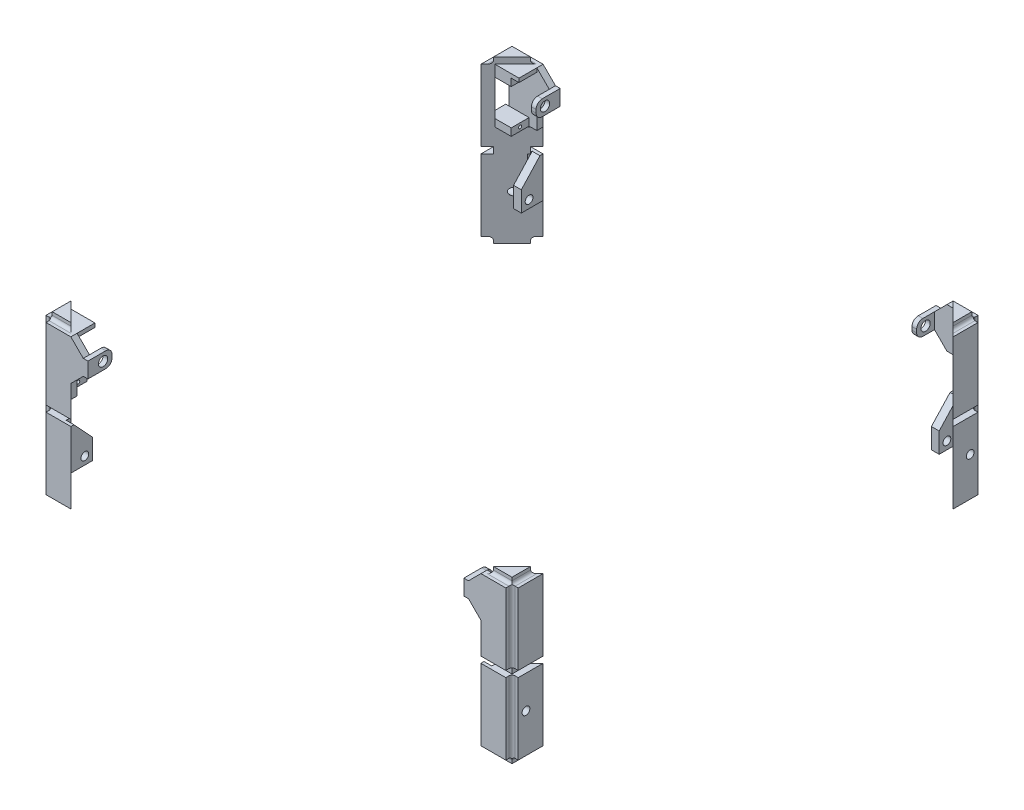
SolidWorks part; units mm, degrees
ref_plane "前基準面" through (0, 0, 0) normal (0, 0, 1) x (1, 0, 0)
ref_plane "上基準面" through (0, 0, 0) normal (0, 1, 0) x (1, 0, 0)
ref_plane "右基準面" through (0, 0, 0) normal (1, 0, 0) x (0, 0, -1)
sketch "草圖1" plane through (0, 0, 0) normal (0, 1, 0) x (1, 0, 0)
  line L8 (-150, -150) -> (150, -150) construction
  line L9 (-150, -150) -> (-150, 150) construction
  line L10 (-150, 150) -> (150, 150) construction
  line L11 (150, -150) -> (150, 150) construction
  line L12 (-150, -150) -> (150, 150) construction
  line L13 (-150, 150) -> (150, -150) construction
  line L15 (-132, -152) -> (-152, -132)
  line L16 (-132, -152) -> (-152, -152)
  line L17 (-152, -152) -> (-152, -132)
  line L18 (-150, -150) -> (-152, -150) construction
  line L19 (-150, -150) -> (-150, -152) construction
  point P0 (0, 0)
  dimension "D1" = 300
  dimension "D2" = 20
  dimension "D3" = 2
extrude "填料-伸長1" add sketch "草圖1" against normal blind 104
sketch "草圖2" plane through (0, 0, 0) normal (0, 1, 0) x (1, 0, 0)
  line L0 (-152, -152) -> (-121.9454, -121.9454) construction
  line L1 (-152, -152) -> (-121.9454, -152)
  line L2 (-152, -152) -> (-152, -121.9454)
  line L3 (-152, -121.9454) -> (-121.9454, -121.9454)
  line L4 (-121.9454, -152) -> (-121.9454, -121.9454)
  line L5 (-148, -148) -> (-125.0092, -148)
  line L6 (-148, -148) -> (-148, -125.0092)
  line L7 (-148, -125.0092) -> (-125.0092, -125.0092)
  line L8 (-125.0092, -148) -> (-125.0092, -125.0092)
  point P9 (0, 0)
  point P10 (0, 0)
  dimension "D1" = 4
  dimension "D2" = 4
extrude "除料-伸長1" cut sketch "草圖2" against normal blind 4
sketch "草圖3" plane through (0, 0, 0) normal (0, 1, 0) x (1, 0, 0)
  line L1 (-148, -148) -> (-152, -148)
  line L2 (-148, -148) -> (-148, -152)
  line L3 (-148, -152) -> (-152, -152)
  line L4 (-152, -148) -> (-152, -152)
extrude "除料-伸長2" cut sketch "草圖3" against normal through all
sketch "草圖12" plane through (0, -104, 0) normal (0, -1, 0) x (1, 0, 0)
  line L0 (-132, 152) -> (-132, 148)
  line L1 (-132, 148) -> (-148, 148)
  line L2 (-148, 148) -> (-148, 132)
  line L3 (-148, 132) -> (-152, 132)
  line L4 (-152, 132) -> (-152, 152)
  line L5 (-152, 152) -> (-132, 152)
extrude "除料-伸長7" cut sketch "草圖12" against normal blind 4
fillet "圓角2" radius 2 1 edges at (-148, -52, 148)
fillet "圓角3" radius 2 4 edges at (-142, -4, 148) (-148, -4, 142) (-148, -100, 142) (-142, -100, 148)
ref_plane "平面1" through (0, -54, 0) normal (0, 1, 0) x (1, 0, 0)
sketch "草圖4" plane through (0, -54, 0) normal (0, 1, 0) x (1, 0, 0)
  line L1 (-148, -148) -> (-132, -148)
  line L3 (-152, -152) -> (-132, -152)
  line L4 (-132, -148) -> (-132, -152)
  line L8 (-148, -148) -> (-148, -132)
  line L9 (-148, -132) -> (-152, -132)
  line L10 (-152, -152) -> (-152, -132)
  point P2 (0, 0)
  point P5 (0, 0)
  point P6 (-133.2619, -151.1784)
  point P7 (0, 0)
  point P8 (0, 0)
  point P13 (0, 0)
  point P14 (0, 0)
  point P15 (-152, -152)
  point P16 (-152.1934, -152)
  point P19 (-146.8025, -146.9401)
  point P21 (0, 0)
  point P22 (-146.9952, -147.1603)
  point P24 (0, 0)
  point P25 (0, 0)
  point P26 (-152, -132)
  point P28 (-132, -152)
extrude "除料-伸長3" cut sketch "草圖4" along normal blind 4
sketch "草圖6" plane through (0, 0, 152) normal (0, 0, 1) x (1, 0, 0)
  line L5 (-132, -80) -> (-137, -80)
  line L6 (-132, -80) -> (-132, -54)
  line L7 (-132, -54) -> (-137, -54)
  line L8 (-137, -80) -> (-137, -54)
  line L12 (-132, -100) -> (-132, -54) construction
  point P0 (-132, -56.72)
  point P12 (0, 0)
  point P13 (0, 0)
  point P14 (-148, -78.2968)
  point P15 (-148, -80)
  point P16 (0, 0)
  point P18 (0, 0)
  point P20 (0, 0)
  dimension "D1" = 26
  dimension "D2" = 5
extrude "填料-伸長2" add sketch "草圖6" against normal blind 14
sketch "草圖7" plane through (-132, 0, 0) normal (-1, 0, 0) x (0, 0, 1)
  line L0 (152, -80) -> (152, -54) construction
  line L1 (138, -80) -> (152, -80) construction
  line L2 (143, -75) -> (143, -80) construction
  line L4 (138, -67) -> (150, -54)
  line L5 (6.6, -54) -> (-6.6, -54) construction
  line L6 (150, -54) -> (138, -54)
  line L7 (138, -54) -> (138, -67)
  line L10 (138, -80) -> (138, -54) construction
  line L15 (138, -54) -> (152, -54) construction
  circle A0 centre (143, -75) radius 2.5
  point P4 (0, 0)
  point P6 (143, -77.5394)
  point P12 (0, 0)
  point P15 (153.4829, -54)
  point P16 (0, 0)
  point P17 (162, -42)
  point P18 (0, 0)
  point P19 (0, 0)
  point P21 (0, 0)
  point P22 (162, -54)
  point P23 (0, 0)
  point P24 (0, 0)
  point P25 (0, 0)
  point P28 (0, 0)
  point P29 (0, 0)
  point P30 (0, 0)
  point P31 (0, 0)
  point P35 (0, 0)
  dimension "D2" = 5
  dimension "D1" = 5
  dimension "D3" = 2
  dimension "D4" = 5
extrude "除料-伸長4" cut sketch "草圖7" along normal up to vertex (5 mm away)
sketch "草圖18" plane through (-132, 0, 0) normal (1, 0, 0) x (0, 0, -1)
  circle A0 centre (-143, -75) radius 2.5
  circle A1 centre (-143, -75) radius 2.5 construction
extrude "除料-伸長10" cut sketch "草圖18" against normal up to surface (20 mm away) up to face at (-152, -77, 140)
sketch "草圖8" plane through (0, 0, 152) normal (0, 0, 1) x (1, 0, 0)
  line L1 (-121, -22) -> (-124, -22)
  line L2 (-121, -22) -> (-121, -12)
  line L3 (-121, -12) -> (-124, -12)
  line L4 (-124, -22) -> (-124, -12)
  line L7 (-148, -4) -> (-132, -4) construction
  line L8 (-148, -50) -> (-148, -4) construction
  point P8 (0, 0)
  point P9 (0, 0)
  dimension "D1" = 3
  dimension "D2" = 10
  dimension "D3" = 8
  dimension "D4" = 24
extrude "填料-伸長3" add sketch "草圖8" against normal blind 15.5
sketch "草圖15" plane through (0, 0, 152) normal (0, 0, 1) x (1, 0, 0)
  line L1 (-136, -4) -> (-136, -30)
  line L4 (-124, -22) -> (-124, -12)
  line L5 (-148, -4) -> (-132, -4) construction
  line L6 (-136, 0) -> (-136, -2) construction
  line L7 (-136, -4) -> (-132, -4)
  line L8 (-132, -4) -> (-124, -12)
  line L9 (-136, -30) -> (-132, -30)
  line L10 (-132, -50) -> (-132, -4) construction
  line L11 (-132, -30) -> (-124, -22)
extrude "填料-伸長6" add sketch "草圖15" against normal blind 4
sketch "草圖9" plane through (-121, 0, 0) normal (-1, 0, 0) x (0, 0, 1)
  line L3 (136.5, -22) -> (136.5, -12) construction
  circle A0 centre (142.25, -17) radius 3
  point P6 (142.981, -17)
  point P13 (141.2253, -17)
  dimension "D1" = 6
  dimension "D2" = 13
  dimension "D3" = 5.75
extrude "除料-伸長5" cut sketch "草圖9" along normal up to surface (3 mm away) up to face at (-124, -17, 142.25)
fillet "圓角1" radius 4 2 edges at (-122.5, -22, 136.5) (-122.5, -12, 136.5)
mirror "鏡射2" about plane through (0, 0, 0) normal (1, 0, 0) of bodies 109 106
sketch "草圖14" plane through (0, -4, 0) normal (0, 1, 0) x (1, 0, 0)
  line L1 (-132, -152) -> (-148, -152)
  line L2 (-132, -152) -> (-132, -136.5)
  line L3 (-132, -136.5) -> (-148, -136.5)
  line L4 (-148, -152) -> (-148, -136.5)
  point P4 (0, 0)
  point P5 (0, 0)
  dimension "D1" = 15.5
  dimension "D2" = 16
extrude "填料-伸長5" add sketch "草圖14" against normal blind 35
sketch "草圖13" plane through (0, 0, 148) normal (0, 0, 1) x (1, 0, 0)
  line L0 (-152, -50) -> (-152, -4) construction
  line L1 (-152, -11.25) -> (-137, -11.25)
  line L2 (-152, -11.25) -> (-152, -34.25)
  line L3 (-152, -34.25) -> (-137, -34.25)
  line L5 (-137, -34.25) -> (-137, -39)
  line L6 (-137, -6.5) -> (-132, -6.5)
  line L7 (-137, -6.5) -> (-137, -11.25)
  line L8 (-137, -39) -> (-132, -39)
  line L9 (-132, -6.5) -> (-132, -11.25)
  line L10 (-132, -11.25) -> (-129.0734, -11.25)
  line L12 (-132, -34.25) -> (-129.0734, -34.25)
  line L13 (-129.0734, -11.25) -> (-129.0734, -34.25)
  line L14 (-132, -34.25) -> (-132, -39)
  line L15 (-148, -4) -> (-132, -4) construction
  point P14 (-129.0734, -17)
  dimension "D1" = 23
  dimension "D2" = 15
  dimension "D3" = 5
  dimension "D5" = 32.5
  dimension "D6" = 5.75
  dimension "D7" = 13
extrude "除料-伸長8" cut sketch "草圖13" against normal blind 11.5
sketch "草圖17" plane through (-137, 0, 0) normal (1, 0, 0) x (0, 0, -1)
  line L0 (-142.25, -6.5) -> (-142.25, -39) construction
  line L1 (-136.5, -6.5) -> (-148, -6.5) construction
  line L3 (-142.25, -8.95) -> (-142.25, -36.55) construction
  line L4 (-136.5, -34.25) -> (-148, -34.25) construction
  line L5 (-136.5, -39) -> (-147, -39) construction
  circle A0 centre (-142.25, -8.95) radius 1
  circle A1 centre (-142.25, -36.55) radius 1
  point P10 (-142.25, -22.75)
  point P11 (-142.25, -13.2247)
  point P12 (0, 0)
  point P13 (-142.25, -34.25)
  point P14 (-142.25, -40.0599)
  point P15 (0, 0)
  dimension "D1" = 2
  dimension "D2" = 27.6
extrude "除料-伸長9" cut sketch "草圖17" against normal blind 5
mirror "鏡射3" about plane through (0, 0, 0) normal (0, 0, 1) of bodies 119 107 111
